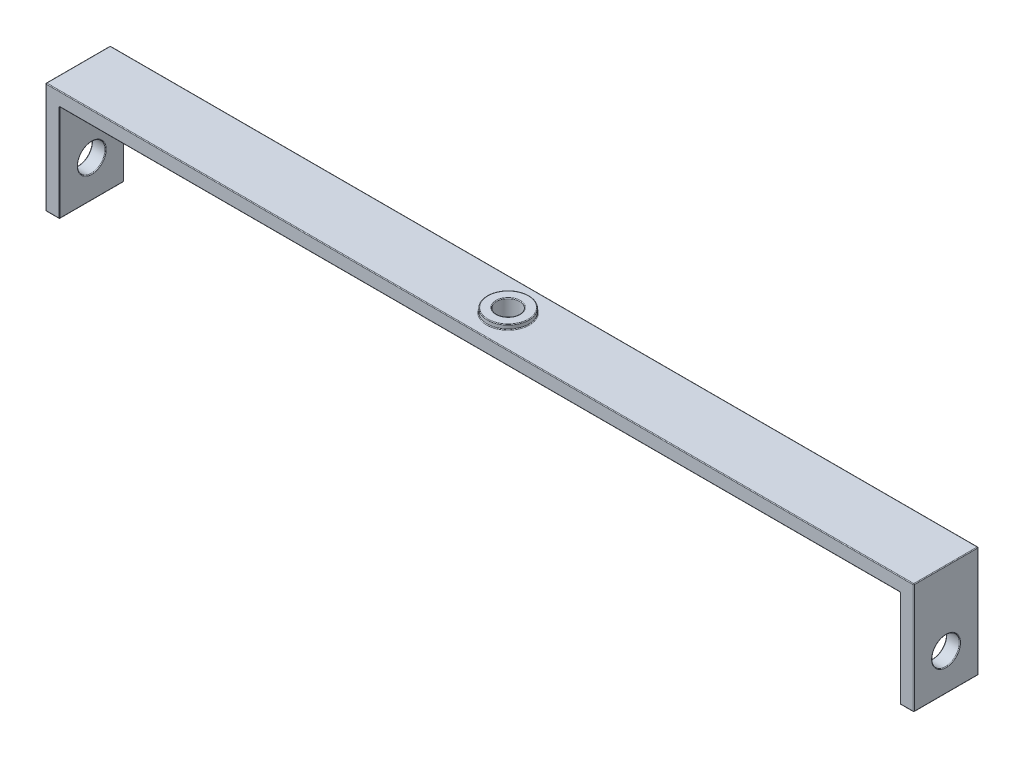
SolidWorks part; units mm, degrees
ref_plane "Front Plane" through (0, 0, 0) normal (0, 0, 1) x (1, 0, 0)
ref_plane "Top Plane" through (0, 0, 0) normal (0, 1, 0) x (1, 0, 0)
ref_plane "Right Plane" through (0, 0, 0) normal (1, 0, 0) x (0, 0, -1)
sketch "Sketch1" plane through (0, 0, 0) normal (0, 0, 1) x (1, 0, 0)
  line L0 (-46.5791, 0) -> (47.4209, 0)
  line L1 (47.4209, 0) -> (47.4209, -12)
  line L2 (-46.5791, 0) -> (-46.5791, -12)
  line L3 (-45.0791, -1.5) -> (-45.0791, -12)
  line L4 (-45.0791, -1.5) -> (45.9209, -1.5)
  line L5 (45.9209, -1.5) -> (45.9209, -12)
  line L6 (-46.5791, -12) -> (-45.0791, -12)
  line L7 (45.9209, -12) -> (47.4209, -12)
  dimension "D1" = 94
  dimension "D2" = 12
  dimension "D3" = 1.5
extrude "Boss-Extrude2" add sketch "Sketch1" along normal blind 3.5 and the other way blind 3.5
sketch "Sketch3" plane through (0, 0, 0) normal (0, 1, 0) x (1, 0, 0)
  circle A0 centre (0, 0) radius 1.25
  dimension "D1" = 2.5
extrude "Cut-Extrude6" cut sketch "Sketch3" against normal up to surface (1.5 mm away) up to face at (0.4209, -1.5, 0)
sketch "Sketch4" plane through (0, 0, 0) normal (0, 1, 0) x (1, 0, 0)
  circle A0 centre (0, 0) radius 1.25 construction
  circle A1 centre (0, 0) radius 1.25
  circle A2 centre (0, 0) radius 2.25
  dimension "D1" = 1
extrude "Boss-Extrude3" add sketch "Sketch4" along normal blind 0.5
sketch "Sketch5" plane through (0, 0, 0) normal (1, 0, 0) x (0, 0, -1)
  line L0 (0, 0.5) -> (0, -8) construction
  line L1 (1.25, 0.5) -> (-1.25, 0.5) construction
  circle A0 centre (0, -8) radius 1.5
  dimension "D2" = 3
  dimension "D1" = 8.5
extrude "Cut-Extrude9" cut sketch "Sketch5" against normal up to surface and the other way up to surface up to face at (-46.5791, -6, 0) other way up to face at (47.4209, -6, 0)
fillet "Fillet6" radius 0.075 32 edges at (47.4209, -8, -1.5) (-46.5791, -8, 1.5) (-45.0791, -8, -1.5) (45.9209, -8, 1.5) (0, 0.5, 1.25) (0, 0, 2.25) (0, 0.5, 2.25) (0, -1.5, -1.25) (-46.5791, -6, 3.5) (-45.8291, -12, 3.5) (-45.0791, -6.75, 3.5) (0.4209, -1.5, 3.5) (45.9209, -6.75, 3.5) (46.6709, -12, 3.5) (47.4209, -6, 3.5) (-46.5791, -6, -3.5) (-45.8291, -12, -3.5) (-45.0791, -6.75, -3.5) (0.4209, -1.5, -3.5) (45.9209, -6.75, -3.5) (46.6709, -12, -3.5) (47.4209, -6, -3.5) (0.4209, 0, -3.5) (-46.5791, -12, 0) (-45.0791, -12, 0) (-45.0791, -1.5, 0) (45.9209, -1.5, 0) (45.9209, -12, 0) (47.4209, -12, 0) (47.4209, 0, 0) (-46.5791, 0, 0) (0.4209, 0, 3.5)
